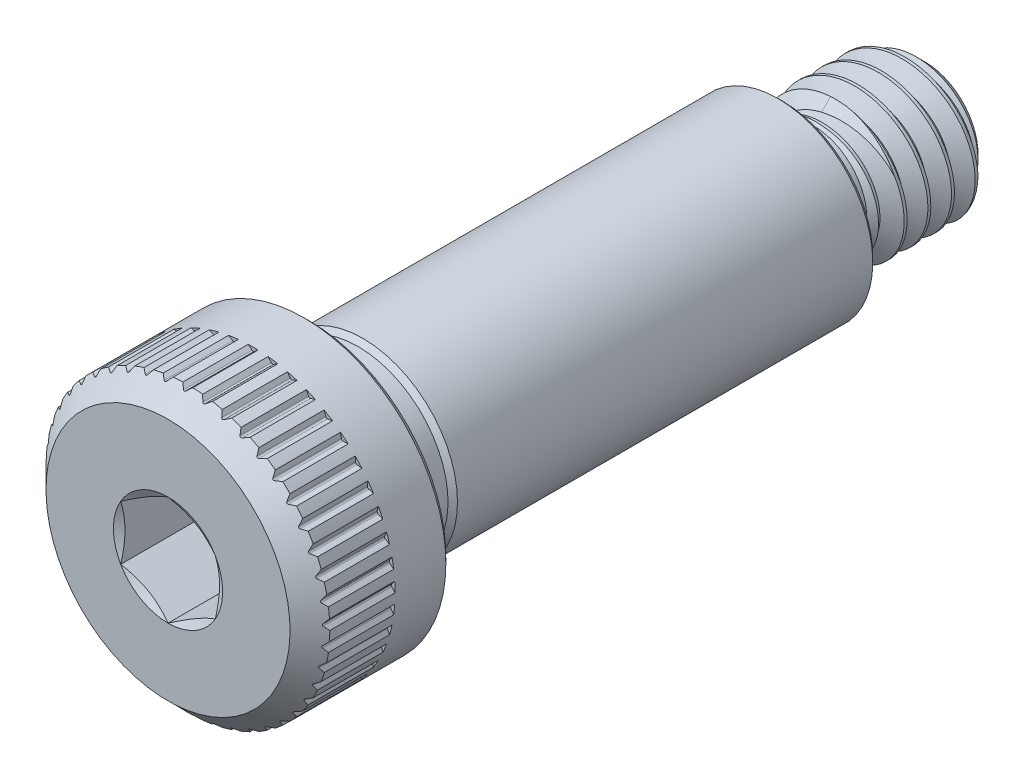
SolidWorks part; units mm, degrees
ref_plane "Front Plane" through (0, 0, 0) normal (0, 0, 1) x (1, 0, 0)
ref_plane "Top Plane" through (0, 0, 0) normal (0, 1, 0) x (1, 0, 0)
ref_plane "Right Plane" through (0, 0, 0) normal (1, 0, 0) x (0, 0, -1)
sketch "Sketch1" plane through (0, 0, 0) normal (0, 0, 1) x (1, 0, 0)
  line L1 (0, 1.1547) -> (-1, 0.5774)
  line L2 (-1, 0.5774) -> (-1, -0.5774)
  line L3 (-1, -0.5774) -> (0, -1.1547)
  line L4 (0, -1.1547) -> (1, -0.5774)
  line L5 (1, -0.5774) -> (1, 0.5774)
  line L6 (1, 0.5774) -> (0, 1.1547)
  circle A0 centre (0, 0) radius 3
  circle A1 centre (0, 0) radius 1 construction
  point P3 (0, 3)
  point P11 (0, -3)
  dimension "Head Diameter" = 6
  dimension "Drive Size" = 2
sketch "Sketch2" plane through (0, 0, 0) normal (1, 0, 0) x (0, 0, -1)
  line L0 (-8, 0) -> (8, 0) construction
  point P2 (0, 0)
  point P4 (-5, 0)
  point P5 (5, 0)
  point P6 (-5, -3)
  point P7 (-5, 3)
  point P9 (5, 3)
  dimension "Head Height" = 3
  dimension "Thread Length" = 3
  dimension "Shoulder Length" = 10
sketch "Sketch3" plane through (0, 0, 0) normal (1, 0, 0) x (0, 0, -1)
  line L0 (-8, 0) -> (-8, 3)
  line L1 (-8, 3) -> (-5, 3)
  line L2 (-5, 3) -> (-5, 0)
  line L3 (-8, 0) -> (-5, 0) construction
  line L4 (-8, 2.58) -> (-7.58, 3)
  line L5 (-5.126, 3) -> (-5, 2.874)
  point P4 (-6.35, 0)
  point P10 (-6.2, 3)
  dimension "D1" = 45
  dimension "D4" = 1.65
  dimension "D5" = 0.42
  dimension "D6" = 0.126
  dimension "D2" = 1.8
sketch "Sketch4" plane through (0, 0, 0) normal (1, 0, 0) x (0, 0, -1)
  line L0 (-5, 1.9) -> (-3.98, 1.9)
  line L1 (-5, 3) -> (-5, 0) construction
  line L2 (-3.98, 1.9) -> (-3.88, 2)
  line L3 (-3.88, 2) -> (4.9, 2)
  line L4 (-3.88, 2) -> (-3.88, 0)
  line L5 (-8, 0) -> (8, 0) construction
  line L6 (-5, 0) -> (-3.88, 0) construction
  line L7 (4.9, 2) -> (5, 1.9)
  line L8 (5, 1.9) -> (5, 0)
  line L9 (-3.88, 0) -> (5, 0) construction
  dimension "D1" = 45
  dimension "Head Undercut Width (J)" = 1.12
  dimension "Shoulder Diameter" = 4
  dimension "D2" = 3.8
sketch "Sketch5" plane through (0, 0, 0) normal (1, 0, 0) x (0, 0, -1)
  line L0 (5, 0) -> (8, 0) construction
  line L1 (8, 0) -> (8, 1.5)
  line L2 (8, 1.5) -> (6.025, 1.5)
  line L3 (6.025, 1.5) -> (5.65, 1.125)
  line L4 (5.65, 1.125) -> (5, 1.125)
  line L5 (5, 1.9) -> (5, 0) construction
  line L6 (7.625, 1.5) -> (8, 1.125)
  point P4 (7.5, 0)
  point P13 (7.25, 1.5)
  point P16 (7.25, -1.5)
  point P21 (8, -1.5)
  point P22 (8, 1.5)
  dimension "Thread Diameter" = 3
  dimension "Thread Pitch" = 0.5
  dimension "D1" = 45
  dimension "D2" = 0.375
  dimension "Thread Undercut Width (M)" = 0.65
  dimension "D3" = 0.75
sketch "Sketch6" plane through (0, 0, 0) normal (1, 0, 0) x (0, 0, -1)
  line L0 (-8, 0) -> (-8, 2.58)
  line L1 (-8, 2.58) -> (-7.58, 3)
  line L2 (-7.58, 3) -> (-5.126, 3)
  line L3 (-5, 2.874) -> (-5, 2.1)
  line L4 (-4.8, 1.9) -> (-3.98, 1.9)
  line L5 (-3.98, 1.9) -> (-3.88, 2)
  line L6 (-3.88, 2) -> (4.9, 2)
  line L7 (4.9, 2) -> (5, 1.9)
  line L8 (5, 1.9) -> (5, 1.3125)
  line L9 (5.1875, 1.125) -> (5.65, 1.125)
  line L10 (5.65, 1.125) -> (6.025, 1.5)
  line L11 (6.025, 1.5) -> (7.625, 1.5)
  line L12 (7.625, 1.5) -> (8, 1.125)
  line L13 (8, 1.125) -> (8, 0)
  line L14 (8, 0) -> (-8, 0)
  line L15 (-5.126, 3) -> (-5, 2.874) construction
  line L16 (-5.126, 3) -> (-5, 2.874)
  line L17 (-4.8, 2.1) -> (-4.8, 1.9) construction
  line L18 (5.1875, 1.125) -> (5.1875, 1.5) construction
  arc A0 (-5, 2.1) -> (-4.8, 1.9) centre (-4.8, 2.1) ccw
  arc A1 (5, 1.3125) -> (5.1875, 1.125) centre (5.1875, 1.3125) ccw
  point P34 (-4.8, 2)
  point P37 (5.1875, 1.3125)
revolve "Revolve1" add sketch "Sketch6" angle 360 about L14
sketch "Sketch7" plane through (0, 0, 8) normal (0, 0, 1) x (1, 0, 0)
  line L0 (0, -1.1547) -> (1, -0.5774) construction
  line L1 (-1, -0.5774) -> (0, -1.1547) construction
  line L2 (-1, 0.5774) -> (-1, -0.5774) construction
  line L3 (0, 1.1547) -> (-1, 0.5774) construction
  line L4 (1, 0.5774) -> (0, 1.1547) construction
  line L5 (1, -0.5774) -> (1, 0.5774) construction
  line L6 (0, -1.1547) -> (1, -0.5774)
  line L7 (-1, -0.5774) -> (0, -1.1547)
  line L8 (-1, 0.5774) -> (-1, -0.5774)
  line L9 (0, 1.1547) -> (-1, 0.5774)
  line L10 (1, 0.5774) -> (0, 1.1547)
  line L11 (1, -0.5774) -> (1, 0.5774)
extrude "Cut-Extrude1" cut sketch "Sketch7" against normal up to vertex (1.65 mm away) up to point (0, 0, 6.35)
sketch "Sketch8" plane through (0, 0, 8) normal (0, 0, 1) x (1, 0, 0)
  circle A0 centre (0, 0) radius 1.1547
extrude "Cut-Extrude2" cut sketch "Sketch8" against normal up to vertex (1.65 mm away) draft 60 up to point (0, 0, 6.35)
ref_plane "Plane1" through (0, 0, -5.65) normal (0, 0, 1) x (1, 0, 0)
split "Split1" trim tools "Plane1" bodies to split 106 resulting bodies 107 108
sketch "Sketch10" plane through (0, 0, -8) normal (0, 0, -1) x (-1, 0, 0)
  circle A0 centre (0, 0) radius 1.5 construction
  circle A1 centre (0, 0) radius 1.5
curve "Helix/Spiral1" pitch 0.5 height 3.5 radius 1.5 centre (0, 0, -8) axis (0, 0, 1) start towards (0, 1, 0)
sketch "Sketch11" plane through (0, 0, 0) normal (1, 0, 0) x (0, 0, -1)
  line L0 (7.9688, 1.5541) -> (8.2188, 1.1211) construction
  line L1 (8.2188, 1.1211) -> (8.4688, 1.5541) construction
  line L2 (8.4688, 1.5541) -> (7.9688, 1.5541) construction
  line L3 (7.9844, 1.5271) -> (8.4531, 1.5271)
  line L4 (8.4531, 1.5271) -> (8.25, 1.1752)
  line L5 (8.25, 1.1752) -> (8.1875, 1.1752)
  line L6 (8.1875, 1.1752) -> (7.9844, 1.5271)
  line L7 (8.2188, 1.1752) -> (8.2188, 1.1211) construction
  line L8 (8, 1.5) -> (8.4375, 1.5) construction
  line L9 (8.2188, 1.5541) -> (8.2188, 1.5) construction
  point P12 (8.2188, 1.5271)
  dimension "D1" = 0.5
  dimension "D2" = 0.0625
sweep "Cut-Sweep1" cut profiles "Sketch11" path "Helix/Spiral1" align with end faces yes
combine bodies "Combine1" operation type add bodies to combine 109 108
sketch "Sketch12" plane through (0, 0, 8) normal (0, 0, 1) x (1, 0, 0)
  line L0 (0, 0) -> (-0.1047, 2.9982) construction
  line L1 (0, 0) -> (0.1047, 2.9982) construction
  line L2 (0, 0) -> (0, 2.58) construction
  line L6 (0, 3) -> (0, 2.895) construction
  line L7 (0, 2.895) -> (0, 2.79) construction
  line L10 (0, 3) -> (0, 3.105) construction
  line L11 (0, 2.79) -> (0, 2.685) construction
  line L12 (0, 2.685) -> (0, 2.58) construction
  line L13 (-0.1069, 3) -> (0.1069, 3)
  line L14 (-0.1069, 3) -> (-0.0245, 2.9309)
  line L15 (0.1069, 3) -> (0.0245, 2.9309)
  line L19 (-0.1047, 2.9982) -> (-0.1047, 2.9728) construction
  line L20 (-0.1047, 2.9728) -> (-0.1047, 2.9475) construction
  circle A0 centre (0, 0) radius 3 construction
  circle A1 centre (0, 0) radius 3 construction
  circle A2 centre (0, 0) radius 2.58 construction
  arc A3 (-0.0245, 2.9309) -> (0.0245, 2.9309) centre (0, 2.9602) ccw
  point P7 (0, 3)
  point P15 (0, 2.9475)
  point P26 (0, 2.9475)
  point P28 (-0.1047, 2.9602)
  dimension "D3" = 50
extrude "Cut-Extrude3" cut sketch "Sketch12" against normal up to vertex (1.8 mm away) up to point (0, 3, 6.2)
pattern_circular "CirPattern1" count 45 over 360 about axis through (0, 0, 8) along (0, 0, -1) of "Cut-Extrude3"
equation "\"D2@Sketch5\"=0.75*\"Thread Pitch@Sketch5\""
equation "\"D4@Helix/Spiral1\"=\"Thread Pitch@Sketch5\""
equation "\"D2@Sketch11\"=\"D1@Sketch11\"/8"
equation "\"D1@Sketch11\"=\"Thread Pitch@Sketch5\""
equation "\"D1@CirPattern1\"=360/(2*2*\"D1@Sketch12\")"
equation "\"D3@Sketch5\"=\"Thread Pitch@Sketch5\"*1.5"
equation "\"D4@Sketch3\"=0.55*\"Head Height@Sketch2\""
equation "\"D5@Sketch3\"=.07*\"Head Diameter@Sketch1\""
equation "\"D6@Sketch3\"=0.3*\"D5@Sketch3\""
equation "\"D2@Sketch4\" = 0.95 * \"Shoulder Diameter@Sketch4\""
equation "\"Head Undercut Width (J)@Sketch4\" = 0.28 * \"Shoulder Diameter@Sketch4\""
equation "\"Thread Undercut Width (M)@Sketch5\"=1.3*\"Thread Pitch@Sketch5\""
equation "\"D2@Sketch12\"=\"D1@Sketch12\""
equation "\"D2@Sketch3\"=0.6*\"Head Height@Sketch2\""
equation "\"D5@Helix/Spiral1\"=round(\"Thread Length@Sketch2\"/\"Thread Pitch@Sketch5\")+1"
